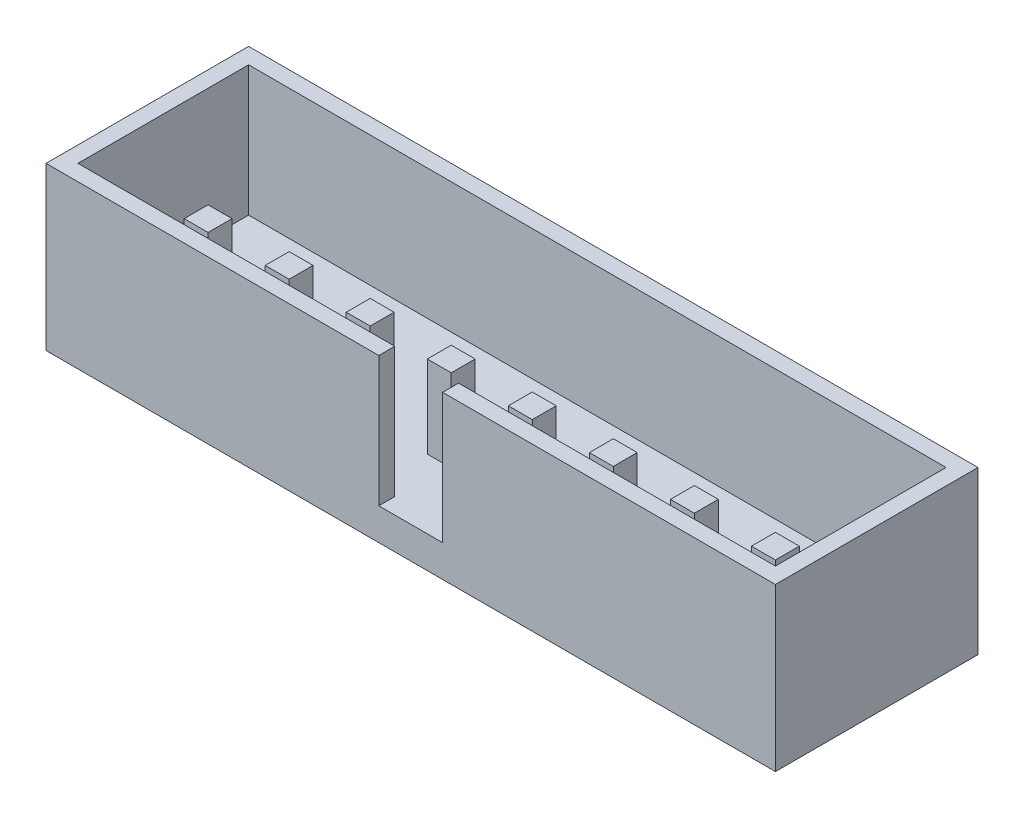
SolidWorks part; units mm, degrees
ref_plane "前视基准面" through (0, 0, 0) normal (0, 0, 1) x (1, 0, 0)
ref_plane "上视基准面" through (0, 0, 0) normal (0, 1, 0) x (1, 0, 0)
ref_plane "右视基准面" through (0, 0, 0) normal (1, 0, 0) x (0, 0, -1)
sketch "草图1" plane through (0, 0, 0) normal (0, 1, 0) x (1, 0, 0)
  line L0 (0, 7.1914) -> (0, -5.4429) construction
  line L1 (-11.43, 3.175) -> (11.43, 3.175)
  line L2 (-11.43, 3.175) -> (-11.43, -3.175)
  line L3 (-11.43, -3.175) -> (11.43, -3.175)
  line L4 (11.43, 3.175) -> (11.43, -3.175)
  line L5 (-10.6234, 0) -> (16.1963, 0) construction
  dimension "D1" = 22.86
  dimension "D2" = 6.35
extrude "拉伸1" add sketch "草图1" along normal blind 5.08
sketch "草图2" plane through (0, 5.08, 0) normal (0, 1, 0) x (-1, 0, 0)
  line L8 (10.93, -2.675) -> (10.93, 2.675)
  line L9 (10.93, 2.675) -> (-10.93, 2.675)
  line L10 (-10.93, 2.675) -> (-10.93, -2.675)
  line L11 (-10.93, -2.675) -> (10.93, -2.675)
  line L12 (10.93, -2.675) -> (10.93, 2.675)
  line L13 (10.93, 2.675) -> (-10.93, 2.675)
  line L14 (-10.93, 2.675) -> (-10.93, -2.675)
  line L15 (-10.93, -2.675) -> (10.93, -2.675)
  dimension "D1" = 0.5
extrude "切除-拉伸1" cut sketch "草图2" against normal offset from surface (4.08 mm away) 1 up to face at (0, 0, 0)
sketch "草图3" plane through (0, 0, 3.175) normal (0, 0, 1) x (1, 0, 0)
  line L0 (-11.43, 5.08) -> (11.43, 5.08) construction
  line L1 (-1, 5.08) -> (1, 5.08)
  line L2 (-1, 5.08) -> (-1, 1)
  line L3 (-1, 1) -> (1, 1)
  line L4 (1, 5.08) -> (1, 1)
  line L5 (10.93, 1) -> (-10.93, 1) construction
  line L6 (0, -1.5083) -> (0, 12.2426) construction
  dimension "D1" = 2
extrude "切除-拉伸2" cut sketch "草图3" against normal blind 1
sketch "草图4" plane through (0, 0, 0) normal (0, -1, 0) x (1, 0, 0)
  line L0 (7.6775, 0.635) -> (-8.5467, 0.635) construction
  line L1 (-11.43, 3.175) -> (11.43, 3.175) construction
  line L2 (0, -3.6953) -> (0, 4.0669) construction
  line L3 (-1.27, 2.1009) -> (-1.27, -0.7012) construction
  line L4 (-1.645, 1.01) -> (-0.895, 1.01)
  line L5 (-1.645, 1.01) -> (-1.645, 0.26)
  line L6 (-1.645, 0.26) -> (-0.895, 0.26)
  line L7 (-0.895, 1.01) -> (-0.895, 0.26)
  line L8 (0.895, 1.01) -> (1.645, 1.01)
  line L9 (0.895, 1.01) -> (0.895, 0.26)
  line L10 (0.895, 0.26) -> (1.645, 0.26)
  line L11 (1.645, 1.01) -> (1.645, 0.26)
  line L12 (2.54, -3.6953) -> (2.54, 4.0669) construction
  line L13 (3.435, 1.01) -> (4.185, 1.01)
  line L14 (3.435, 1.01) -> (3.435, 0.26)
  line L15 (3.435, 0.26) -> (4.185, 0.26)
  line L16 (4.185, 1.01) -> (4.185, 0.26)
  line L17 (5.08, -3.6953) -> (5.08, 4.0669) construction
  line L18 (5.975, 1.01) -> (6.725, 1.01)
  line L19 (5.975, 1.01) -> (5.975, 0.26)
  line L20 (5.975, 0.26) -> (6.725, 0.26)
  line L21 (6.725, 1.01) -> (6.725, 0.26)
  line L22 (7.62, -3.6953) -> (7.62, 4.0669) construction
  line L23 (-4.185, 1.01) -> (-3.435, 1.01)
  line L24 (-4.185, 1.01) -> (-4.185, 0.26)
  line L25 (-4.185, 0.26) -> (-3.435, 0.26)
  line L26 (-3.435, 1.01) -> (-3.435, 0.26)
  line L27 (-3.81, 2.1009) -> (-3.81, -0.7012) construction
  line L28 (5.1375, 0.635) -> (-11.0867, 0.635) construction
  line L29 (-6.725, 1.01) -> (-5.975, 1.01)
  line L30 (-6.725, 1.01) -> (-6.725, 0.26)
  line L31 (-6.725, 0.26) -> (-5.975, 0.26)
  line L32 (-5.975, 1.01) -> (-5.975, 0.26)
  line L33 (-6.35, 2.1009) -> (-6.35, -0.7012) construction
  line L34 (2.5975, 0.635) -> (-13.6267, 0.635) construction
  line L35 (-9.265, 1.01) -> (-8.515, 1.01)
  line L36 (-9.265, 1.01) -> (-9.265, 0.26)
  line L37 (-9.265, 0.26) -> (-8.515, 0.26)
  line L38 (-8.515, 1.01) -> (-8.515, 0.26)
  line L39 (-8.89, 2.1009) -> (-8.89, -0.7012) construction
  line L40 (0.0575, 0.635) -> (-16.1667, 0.635) construction
  line L41 (8.515, 1.01) -> (9.265, 1.01)
  line L42 (8.515, 1.01) -> (8.515, 0.26)
  line L43 (8.515, 0.26) -> (9.265, 0.26)
  line L44 (9.265, 1.01) -> (9.265, 0.26)
  line L45 (10.16, -3.6953) -> (10.16, 4.0669) construction
  dimension "D1" = 2.54
  dimension "D2" = 0.75
  dimension "D3" = 0.75
  dimension "D4" = 1.27
  dimension "D5" = 5
  dimension "D6" = 4
extrude "拉伸2" add sketch "草图4" along normal blind 2 and the other way offset from surface 1.5 other way up to face at (0, 5.08, 0.975)
